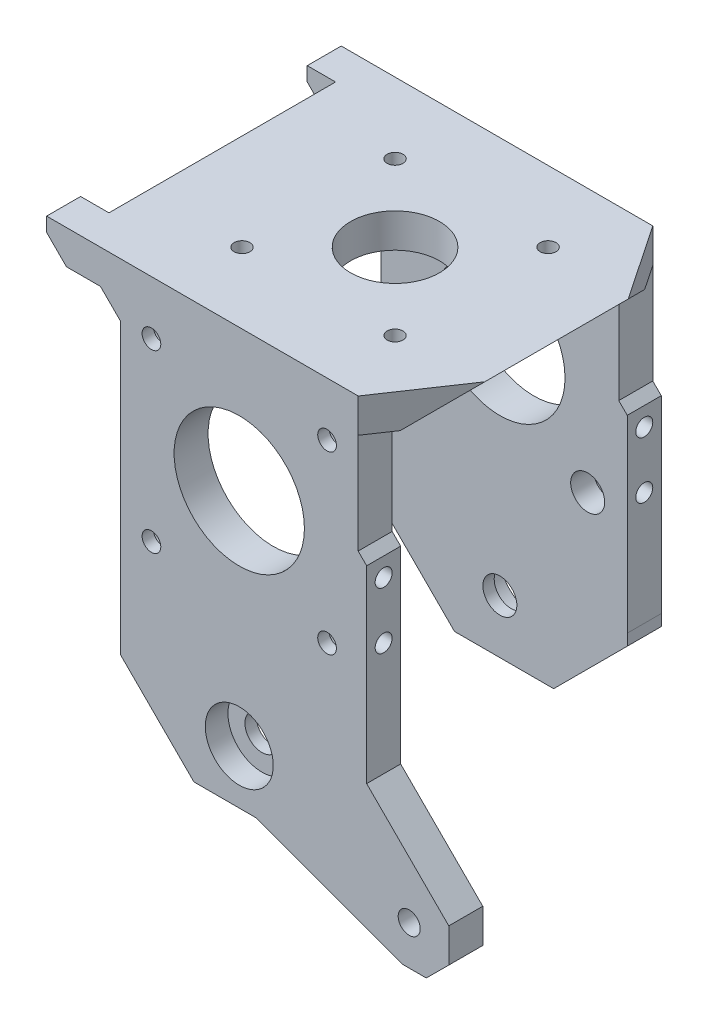
SolidWorks part; units mm, degrees
ref_plane "Front Plane" through (0, 0, 0) normal (0, 0, 1) x (1, 0, 0)
ref_plane "Top Plane" through (0, 0, 0) normal (0, 1, 0) x (1, 0, 0)
ref_plane "Right Plane" through (0, 0, 0) normal (1, 0, 0) x (0, 0, -1)
sketch "Sketch1" plane through (0, 0, 0) normal (0, 0, 1) x (1, 0, 0)
  line L0 (-65.6806, 0) -> (67.5075, 0) construction
  line L1 (0, 51.6446) -> (0, -50.2865) construction
  line L2 (38.003, 38.4634) -> (-25.997, 38.4634)
  line L3 (-25.997, 38.4634) -> (-25.997, 35.9634)
  line L4 (-25.997, 35.9634) -> (-22.4968, 32.4632)
  line L5 (-22.4968, 32.4632) -> (-16.4968, 32.4632)
  line L6 (-16.4968, 32.4632) -> (-12.9966, 28.963)
  line L7 (-12.9966, 28.963) -> (-12.9966, -22.037)
  line L8 (-12.9966, -22.037) -> (0, -35.0336)
  line L9 (0, -35.0336) -> (10.9, -35.0336)
  line L10 (10.9, -35.0336) -> (36.9107, -44.5007)
  line L11 (38.003, 38.4634) -> (31.9926, 32.453)
  line L12 (31.9926, 32.453) -> (28.9926, 32.453)
  line L13 (28.9926, 14.753) -> (30.4917, 13.2539)
  line L14 (30.4917, 13.2539) -> (30.4917, -20.0461)
  line L15 (28.9926, 32.453) -> (28.9926, 14.753)
  line L16 (30.4917, -20.0461) -> (44.9874, -34.5418)
  line L17 (44.9874, -34.5418) -> (44.9874, -40.5418)
  line L18 (36.9107, -44.5007) -> (41.0107, -44.5007)
  line L19 (44.9874, -40.5418) -> (41.0107, -44.5007)
  line L21 (10.9, -35.0336) -> (17.5, -35.0336)
  line L22 (17.5, -35.0336) -> (30.5108, -22.0228)
  line L23 (30.4917, -20.0461) -> (30.5108, -22.0228)
  dimension "D8" = 51
  dimension "D11" = 10.9
  dimension "D1" = 64
  dimension "D2" = 2.5
  dimension "D3" = 4.95
  dimension "D4" = 4.95
  dimension "D5" = 6
  dimension "D6" = 135
  dimension "D7" = 135
  dimension "D9" = 18.38
  dimension "D10" = 135
  dimension "D12" = 27.68
  dimension "D13" = 160
  dimension "D14" = 8.5
  dimension "D15" = 3
  dimension "D16" = 17.7
  dimension "D17" = 45
  dimension "D18" = 33.3
  dimension "D19" = 2.12
  dimension "D20" = 135
  dimension "D21" = 135
  dimension "D22" = 20.5
  dimension "D23" = 17.5
  dimension "D24" = 135
extrude "Boss-Extrude1" add sketch "Sketch1" along normal blind 52 contours L23 L14 L13 L15 L12 L11 L2 L3 L4 L5 L6 L7 L8 L9 L21 L22 region at (8.0846, 4.4295, 0)
extrude "Boss-Extrude3" add sketch "Sketch1<4>" against normal blind 6 from offset 52 contours L16 L23 L22 L21 L10 L18 L19 L17 region at (32.0694, -34.4156, 0)
sketch "Sketch1<4>" plane through (0, 0, 0) normal (0, 0, 1) x (1, 0, 0) same geometry as "Sketch1"
ref_plane "Plane1" through (40.4917, 0, 0) normal (1, 0, 0) x (0, 0, -1)
sketch "Sketch8" plane through (40.4917, 0, 0) normal (1, 0, 0) x (0, 0, -1)
  line L0 (0, -35.0336) -> (-6, -35.0336)
  line L1 (-46, -35.0336) -> (0, -35.0336) construction
  line L2 (-6, -35.0336) -> (-6, 32.453)
  line L3 (-52, 32.453) -> (0, 32.453) construction
  line L4 (-6, 32.453) -> (-46, 32.453)
  line L5 (-46, 32.453) -> (-46, -49.8392)
  line L6 (-46, -49.8392) -> (-6, -35.0336)
extrude "Cut-Extrude5" cut sketch "Sketch8" against normal blind 76 contours L5 L6 L2 L4 region at (40.4917, -5.1137, 26.659)
sketch "Sketch9" plane through (0, 38.4634, 0) normal (0, 1, 0) x (1, 0, 0)
  line L0 (38.003, -26) -> (-25.997, -26) construction
  line L1 (38.003, -52) -> (38.003, 0) construction
  line L2 (-25.997, -52) -> (-25.997, 0) construction
  line L3 (-25.997, -52) -> (-25.997, -40)
  line L4 (-25.997, -40) -> (-20.997, -40)
  line L5 (-20.997, -40) -> (-20.997, -12)
  line L6 (-25.997, -52) -> (29.003, -52)
  line L7 (38.003, -52) -> (-25.997, -52) construction
  line L8 (29.003, -52) -> (37.9511, -38.7361)
  line L9 (37.9511, -38.7361) -> (38.003, -26)
  line L10 (29.003, 0) -> (37.9511, -13.2639)
  line L11 (-25.997, -12) -> (-20.997, -12)
  line L12 (-25.997, -12) -> (-37.6258, -26)
  line L13 (-37.6258, -26) -> (-25.997, -40)
  line L14 (29.003, -52) -> (39.4946, -56.914)
  line L15 (39.4946, -56.914) -> (43.2994, -41.1094)
  line L16 (43.2994, -41.1094) -> (37.9511, -38.7361)
  line L17 (37.9511, -13.2639) -> (46.4671, -6.1903)
  line L18 (46.4671, -6.1903) -> (39.703, 3.8363)
  line L19 (39.703, 3.8363) -> (29.003, 0)
  line L20 (-4.0027, -12.4943) -> (9.503, -26) construction
  line L21 (9.503, -4.514) -> (9.503, -38.7361) construction
  circle A0 centre (9.503, -26) radius 7.85
  circle A1 centre (-4.0027, -12.4943) radius 1.4
  circle A2 centre (23.0088, -12.4943) radius 1.4
  circle A3 centre (23.0088, -39.5057) radius 1.4
  circle A4 centre (-4.0027, -39.5057) radius 1.4
  point P18 (-20.997, -26)
  point P37 (9.503, -26)
  line M1 (38.003, 0) -> (-25.997, 0)
  line M2 (-25.997, 0) -> (-25.997, -52)
  line M3 (-25.997, -52) -> (38.003, -52)
  line M4 (38.003, -52) -> (38.003, 0)
  dimension "D1" = 30.5
  dimension "D6" = 15.7
  dimension "D7" = 2.8
  dimension "D2" = 12
  dimension "D3" = 5
  dimension "D4" = 45
  dimension "D5" = 19.1
  dimension "D8" = 4
extrude "Cut-Extrude6" cut sketch "Sketch9" against normal blind 21 contours L10 L17 M4 M1 | L16 L8 M4 M3 | L11 L4 L5 M2 | A0 | A1 | A2 | A3 | A4 region at (-23.497, 38.4634, 26) region at (35.0029, 38.4634, 47.5534) region at (35.0029, 38.4634, 4.4465) region at (9.503, 38.4634, 26) region at (-4.0027, 38.4634, 12.4943) region at (23.0088, 38.4634, 12.4943)
sketch "Sketch14" plane through (0, 0, 52) normal (0, 0, 1) x (1, 0, 0)
  line L0 (-12.9966, 28.963) -> (-12.9966, -22.037) construction
  line L1 (29.003, 38.4634) -> (-25.997, 38.4634) construction
  line L2 (8.0034, 38.4634) -> (8.0034, -36.8131) construction
  line L3 (8.0034, 13.4634) -> (-7.4964, -2.0364) construction
  line L4 (0, -35.0336) -> (10.9, -35.0336) construction
  line L5 (8.0034, -25.5366) -> (38.0028, -37.5355) construction
  circle A0 centre (8.0034, 13.4634) radius 11.5
  circle A1 centre (-7.4964, -2.0364) radius 1.65
  circle A2 centre (-7.4964, 28.9632) radius 1.65
  circle A3 centre (23.5032, 28.9632) radius 1.65
  circle A4 centre (23.5032, -2.0364) radius 1.65
  circle A5 centre (8.0034, -25.5366) radius 3
  circle A6 centre (38.0028, -37.5355) radius 1.95
  point P19 (8.0034, 13.4634)
  dimension "D1" = 23
  dimension "D6" = 3.3
  dimension "D8" = 39
  dimension "D10" = 32.31
  dimension "D12" = 3.9
  dimension "D13" = 6
  dimension "D2" = 21
  dimension "D3" = 25
  dimension "D4" = 45
  dimension "D5" = 21.92
  dimension "D9" = 9.497
  dimension "D11" = 111.8
  dimension "D7" = 4
extrude "Cut-Extrude7" cut sketch "Sketch14" against normal blind 62
sketch "Sketch25" plane through (0, 32.453, 0) normal (0, -1, 0) x (1, 0, 0)
  circle A0 centre (-4.0027, 39.5057) radius 3
  circle A1 centre (23.0088, 39.5057) radius 3
  circle A2 centre (23.0088, 12.4943) radius 3
  circle A3 centre (-4.0027, 12.4943) radius 3
extrude "Cut-Extrude8" cut sketch "Sketch25" against normal blind 3.5
sketch "Sketch26" plane through (0, 0, 0) normal (0, 0, -1) x (-1, 0, 0)
  circle A0 centre (-8.0034, -25.5366) radius 6
extrude "Cut-Extrude9" cut sketch "Sketch26" against normal blind 4
sketch "Sketch27" plane through (0, 0, 52) normal (0, 0, 1) x (1, 0, 0)
  circle A0 centre (8.0034, -25.5366) radius 6
extrude "Cut-Extrude10" cut sketch "Sketch27" against normal blind 4
sketch "Sketch34" plane through (0, 0, 46) normal (0, 0, -1) x (-1, 0, 0)
  circle A0 centre (-23.5032, 28.9632) radius 3
  circle A1 centre (7.4964, 28.9632) radius 3
  circle A2 centre (7.4964, -2.0364) radius 3
  circle A3 centre (-23.5032, -2.0364) radius 3
extrude "Cut-Extrude11" cut sketch "Sketch34" against normal blind 4
sketch "Sketch35" plane through (0, 0, 6) normal (0, 0, 1) x (1, 0, 0)
  circle A0 centre (-7.4964, 28.9632) radius 3
  circle A2 centre (23.5032, -2.0364) radius 3
  circle A3 centre (-7.4964, -2.0364) radius 3
  circle A4 centre (23.5032, 28.9632) radius 3
extrude "Cut-Extrude12" cut sketch "Sketch35" against normal blind 4
sketch "Sketch36" plane through (0, 0, 46) normal (0, 0, -1) x (-1, 0, 0)
  circle A0 centre (-38.0028, -37.5355) radius 4
extrude "Cut-Extrude13" cut sketch "Sketch36" against normal blind 3
sketch "Sketch37" plane through (30.4917, 0, 0) normal (1, 0, 0) x (0, 0, -1)
  line L0 (-3, 13.2539) -> (-3, -5.7877) construction
  line L1 (-6, 13.2539) -> (0, 13.2539) construction
  line L4 (-49, 13.2539) -> (-49, -2.2095) construction
  line L5 (-52, 13.2539) -> (-46, 13.2539) construction
  circle A0 centre (-3, 9.9539) radius 1.5
  circle A2 centre (-3, -0.0461) radius 1.5
  circle A3 centre (-49, 9.9539) radius 1.5
  circle A4 centre (-49, -0.0461) radius 1.5
  dimension "D1" = 3.3
  dimension "D2" = 10
extrude "Cut-Extrude14" cut sketch "Sketch37" against normal blind 5
sketch "Sketch38" plane through (-12.9966, 0, 0) normal (-1, 0, 0) x (0, 0, 1)
  line L0 (49, 28.963) -> (49, -22.037) construction
  line L1 (52, 28.963) -> (46, 28.963) construction
  line L2 (52, -22.037) -> (46, -22.037) construction
  line L3 (3, 28.963) -> (3, -4.3066) construction
  line L4 (6, 28.963) -> (0, 28.963) construction
  circle A0 centre (49, 13.963) radius 1.6
  circle A1 centre (49, 3.963) radius 1.6
  circle A2 centre (3, 13.963) radius 1.6
  circle A3 centre (3, 3.963) radius 1.6
  dimension "D1" = 25
  dimension "D2" = 10
extrude "Cut-Extrude15" cut sketch "Sketch38" against normal blind 4
sketch "Sketch39" plane through (0, 0, 12) normal (0, 0, 1) x (1, 0, 0)
  line L1 (29.003, 38.4634) -> (-25.997, 38.4634) construction
  line L2 (-22.497, 38.4634) -> (-25.997, 38.4634)
  line L3 (-25.997, 38.4634) -> (-28.2765, 32.9704)
  line L4 (-28.2765, 32.9704) -> (-19.1027, 28.6926)
  line L5 (-19.1027, 28.6926) -> (-16.4968, 32.4632)
  line L6 (-16.4968, 32.4632) -> (-20.997, 38.4634)
  line L7 (-20.997, 38.4634) -> (-22.497, 38.4634)
  dimension "D1" = 3.5
extrude "Cut-Extrude16" cut sketch "Sketch39" along normal blind 40 from offset 6 offset against normal yes
